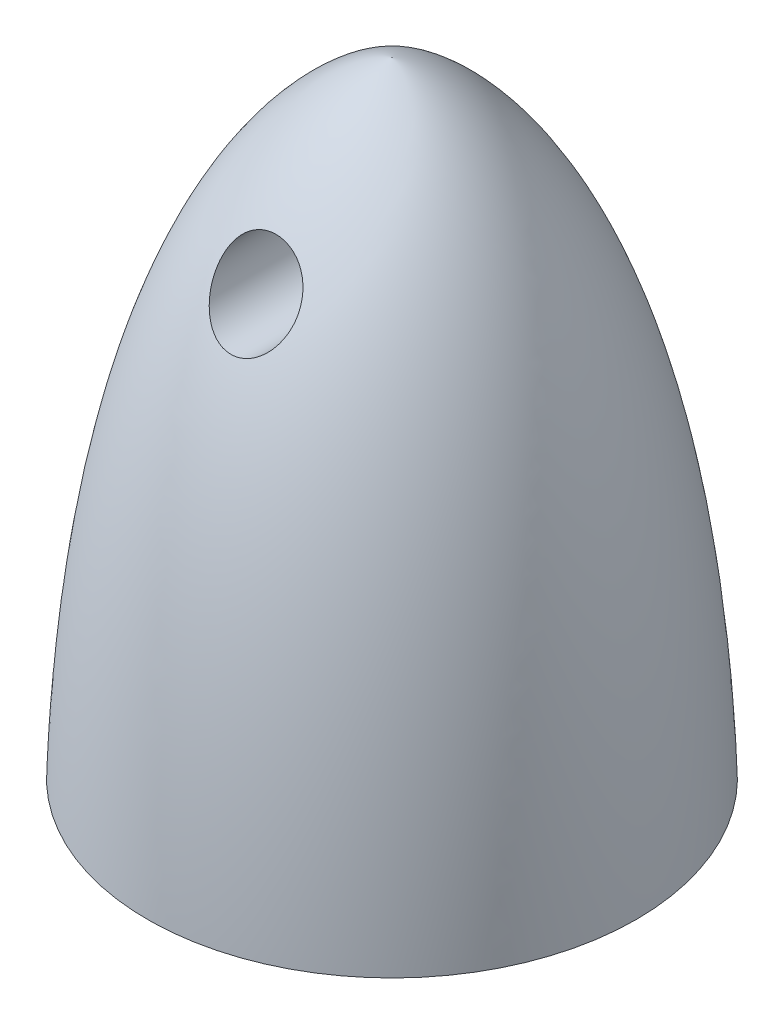
SolidWorks part; units mm, degrees
ref_plane "Front Plane" through (0, 0, 0) normal (0, 0, 1) x (1, 0, 0)
ref_plane "Top Plane" through (0, 0, 0) normal (0, 1, 0) x (1, 0, 0)
ref_plane "Right Plane" through (0, 0, 0) normal (1, 0, 0) x (0, 0, -1)
sketch "Sketch1" plane through (0, 0, 0) normal (0, 0, 1) x (1, 0, 0)
  line L0 (3.5, 3.5284) -> (3.5, 0)
  line L1 (3.5, 0) -> (9, 0)
  line L4 (0, 23) -> (0, 14)
  line L6 (3.5, 3.5284) -> (3.5, 14)
  line L7 (3.5, 14) -> (0, 14)
  line L8 (0, 0) -> (0, 11.9245) construction
  spline S0 degree 3 poles (0, 23) (0.0373, 22.984) (8.2621, 21.4802) (9, 0) knots 0 0 0 0 1 1 1 1
  dimension "D2" = 23
  dimension "D1" = 3.5
  dimension "5.5mm" = 5.5
  dimension "D3" = 14
revolve "Revolve1" add sketch "Sketch1" angle 360 about L8
sketch "Sketch2" plane through (0, 0, 0) normal (0, 1, 0) x (1, 0, 0)
  line L1 (5.6292, 0) -> (2.8146, 4.875)
  line L2 (2.8146, 4.875) -> (-2.8146, 4.875)
  line L3 (-2.8146, 4.875) -> (-5.6292, 0)
  line L4 (-5.6292, 0) -> (-2.8146, -4.875)
  line L5 (-2.8146, -4.875) -> (2.8146, -4.875)
  line L6 (2.8146, -4.875) -> (5.6292, 0)
  circle A0 centre (0, 0) radius 4.875 construction
  dimension "D1" = 9.75
extrude "Cut-Extrude1" cut sketch "Sketch2" along normal blind 7
sketch "Sketch4" plane through (0, 0, 0) normal (0, 0, 1) x (1, 0, 0)
  circle A0 centre (0, 18) radius 1.5
  dimension "D1" = 3
  dimension "D2" = 5
extrude "Cut-Extrude2" cut sketch "Sketch4" against normal mid plane 17
chamfer "Chamfer1" distance 0.5 angle 45 6 edges at (-4.2219, 0, 2.4375) (-4.2219, 0, -2.4375) (0, 0, -4.875) (0, 0, 4.875) (4.2219, 0, 2.4375) (4.2219, 0, -2.4375)
fillet "Fillet1" radius 0.5 2 edges at (3.5, 14, 0) (0, 7, 3.5)
